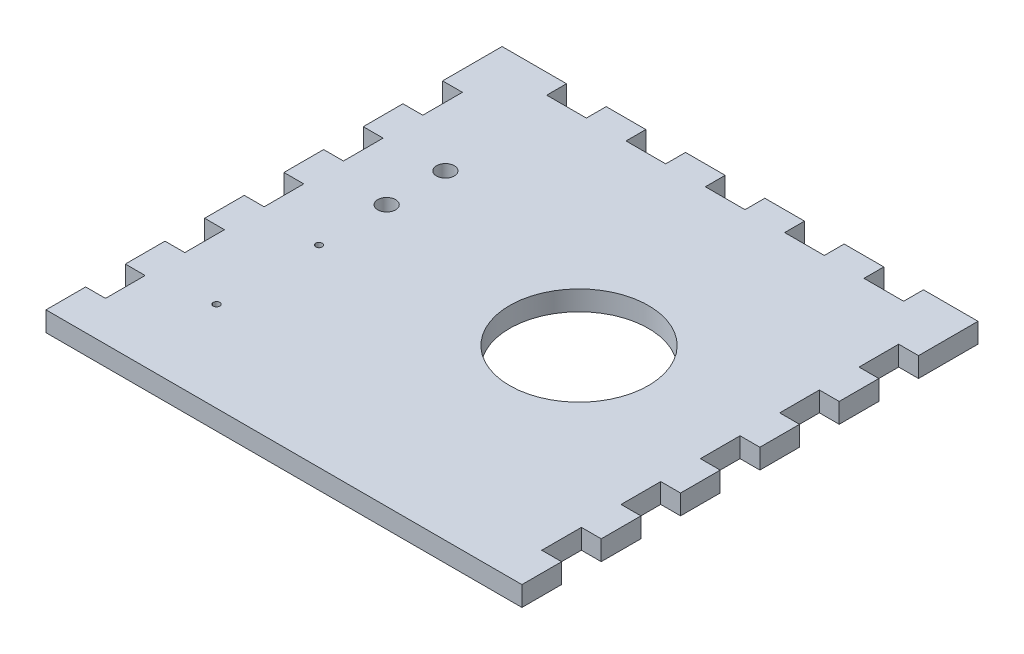
SolidWorks part; units mm, degrees
ref_plane "Front Plane" through (0, 0, 0) normal (0, 0, 1) x (1, 0, 0)
ref_plane "Top Plane" through (0, 0, 0) normal (0, 1, 0) x (1, 0, 0)
ref_plane "Right Plane" through (0, 0, 0) normal (1, 0, 0) x (0, 0, -1)
sketch "Sketch1" plane through (0, 0, 0) normal (0, 1, 0) x (1, 0, 0)
  line L1 (-139.7, -139.7) -> (139.7, -139.7)
  line L2 (-139.7, -139.7) -> (-139.7, 139.7)
  line L3 (-139.7, 139.7) -> (139.7, 139.7)
  line L4 (139.7, -139.7) -> (139.7, 139.7)
  line L5 (-139.7, -139.7) -> (139.7, 139.7) construction
  line L6 (-139.7, 139.7) -> (139.7, -139.7) construction
  point P0 (0, 0)
  dimension "D1" = 279.4
  dimension "D2" = 279.4
extrude "Boss-Extrude1" add sketch "Sketch1" along normal blind 12.7
sketch "Sketch2" plane through (139.7, 0, 0) normal (1, 0, 0) x (0, 0, -1)
  line L0 (-139.7, 12.7) -> (139.7, 12.7) construction
  line L1 (-139.7, 0) -> (-114.3, 0)
  line L2 (-139.7, 0) -> (-139.7, 12.7)
  line L3 (-139.7, 12.7) -> (-114.3, 12.7)
  line L4 (-114.3, 0) -> (-114.3, 12.7)
  dimension "D1" = 25.4
extrude "Boss-Extrude2" add sketch "Sketch2" along normal blind 12.7
pattern_linear "LPattern1" count 6 spacing 50.8 along (0, 0, -1) of "Boss-Extrude2"
mirror "Mirror1" about plane through (0, 0, 0) normal (1, 0, 0) of "LPattern1"
sketch "Sketch3" plane through (0, 0, -139.7) normal (0, 0, -1) x (-1, 0, 0)
  line L0 (-152.4, 12.7) -> (152.4, 12.7) construction
  line L1 (-142.875, 12.7) -> (-117.475, 12.7)
  line L2 (-142.875, 12.7) -> (-142.875, 0)
  line L3 (-142.875, 0) -> (-117.475, 0)
  line L4 (-117.475, 12.7) -> (-117.475, 0)
  line L5 (-152.4, 0) -> (152.4, 0) construction
  line L6 (-152.4, 0) -> (-152.4, 12.7) construction
  dimension "D1" = 9.525
  dimension "D2" = 25.4
extrude "Boss-Extrude3" add sketch "Sketch3" along normal blind 12.7
pattern_linear "LPattern2" count 6 spacing 50.8 along (-1, 0, 0) of "Boss-Extrude3"
sketch "Sketch5" plane through (0, 0, -139.7) normal (0, 0, -1) x (-1, 0, 0)
  line L6 (160.655, 0) -> (-160.655, 0) construction
  line L7 (-152.4, 12.7) -> (-135.3964, 12.7)
  line L8 (-152.4, 12.7) -> (-152.4, 0)
  line L9 (-152.4, 0) -> (-135.3964, 0)
  line L10 (-135.3964, 12.7) -> (-135.3964, 0)
extrude "Boss-Extrude4" add sketch "Sketch5" along normal blind 12.7
mirror "Mirror2" about plane through (0, 0, 0) normal (1, 0, 0) of "Boss-Extrude4"
sketch "Sketch6" plane through (0, 12.7, 0) normal (0, 1, 0) x (1, 0, 0)
  line L0 (66.675, 139.7) -> (41.275, 139.7) construction
  line L1 (139.7, -12.7) -> (139.7, 12.7) construction
  circle A0 centre (38.1, 11.176) radius 44.45
  dimension "D1" = 128.524
  dimension "D2" = 101.6
extrude "Cut-Extrude1" cut sketch "Sketch6" against normal through all
sketch "Sketch7" plane through (0, 12.7, 0) normal (0, 1, 0) x (1, 0, 0)
  line L0 (-139.7, 63.5) -> (-139.7, 38.1) construction
  line L1 (-139.7, 114.3) -> (-139.7, 88.9) construction
  line L2 (-85.725, 139.7) -> (-111.125, 139.7) construction
  circle A0 centre (-101.6, 65.278) radius 5.715
  circle A1 centre (-101.6, 27.686) radius 5.715
  dimension "D1" = 11.43
  dimension "D2" = 11.43
  dimension "D3" = 38.1
  dimension "D4" = 38.1
  dimension "D5" = 37.592
  dimension "D6" = 74.422
extrude "Cut-Extrude2" cut sketch "Sketch7" against normal through all
sketch "Sketch8" plane through (0, 12.7, 0) normal (0, 1, 0) x (1, 0, 0)
  circle A0 centre (-100.9, -81.9861) radius 2.1 construction
  circle A1 centre (-100.9, -81.9861) radius 2.1
  circle A2 centre (-100.9, -16.3789) radius 2.1 construction
  circle A3 centre (-100.9, -16.3789) radius 2.1
extrude "Cut-Extrude3" cut sketch "Sketch8" against normal through all
